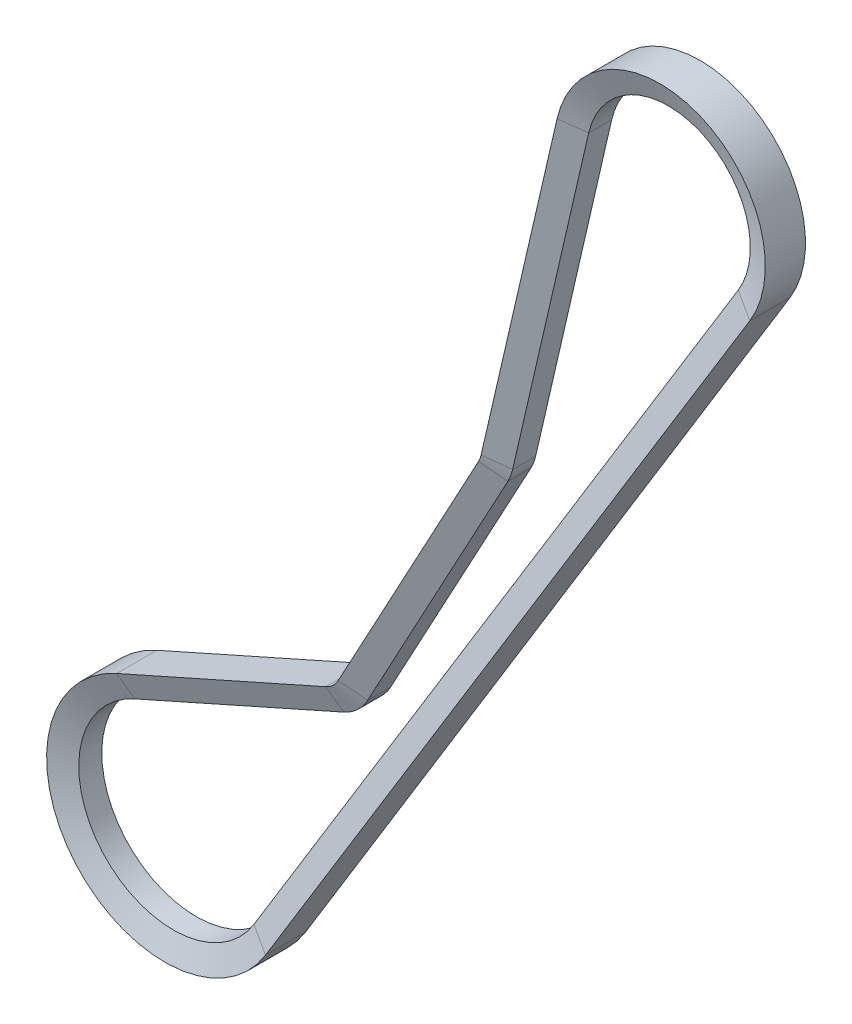
SolidWorks part; units mm, degrees
ref_plane "Front Plane" through (0, 0, 0) normal (0, 0, 1) x (1, 0, 0)
ref_plane "Top Plane" through (0, 0, 0) normal (0, 1, 0) x (1, 0, 0)
ref_plane "Right Plane" through (0, 0, 0) normal (1, 0, 0) x (0, 0, -1)
sketch "Sketch2" plane through (0, 0, 0) normal (0, 0, 1) x (1, 0, 0)
  line L0 (0, 0) -> (1, 0) construction
  line L1 (0, 0) -> (0, 1) construction
  line L12 (21.3243, -13.0489) -> (-93.4955, -200.6853)
  line L14 (-128.7654, -160.4904) -> (-79.2366, -138.4433)
  line L15 (-76.2309, -135.6581) -> (-42.9831, -74.0579)
  line L16 (-42.3838, -72.47) -> (-24.3596, 5.6223)
  arc A4 (-93.4955, -200.6853) -> (-128.7654, -160.4904) centre (-117.3787, -186.0705) cw
  arc A7 (-24.3596, 5.6223) -> (21.3243, -13.0489) centre (0, 0) cw
  arc A8 (-79.2366, -138.4433) -> (-76.2309, -135.6581) centre (-81.819, -132.6421) ccw
  arc A9 (-42.9831, -74.0579) -> (-42.3838, -72.47) centre (-48.5711, -71.0419) ccw
ref_plane "Plane4" through (-24.3596, 5.6223, 0) normal (0.2249, 0.9744, 0) x (0.9744, -0.2249, 0)
sketch "Sketch3" plane through (-24.3596, 5.6223, 0) normal (0.2249, 0.9744, 0) x (0.9744, -0.2249, 0)
  line L0 (0, -4.7625) -> (0, 4.7625)
  line L1 (0, -4.7625) -> (5.588, -2.7286)
  line L2 (5.588, -2.7286) -> (5.588, 2.7286)
  line L3 (5.588, 2.7286) -> (0, 4.7625)
  line L4 (0, 0) -> (5.588, 0) construction
  dimension "D1" = 9.525
  dimension "D2" = 5.588
  dimension "D3" = 40
sweep "Sweep1" add profiles "Sketch3" path "Sketch2"
